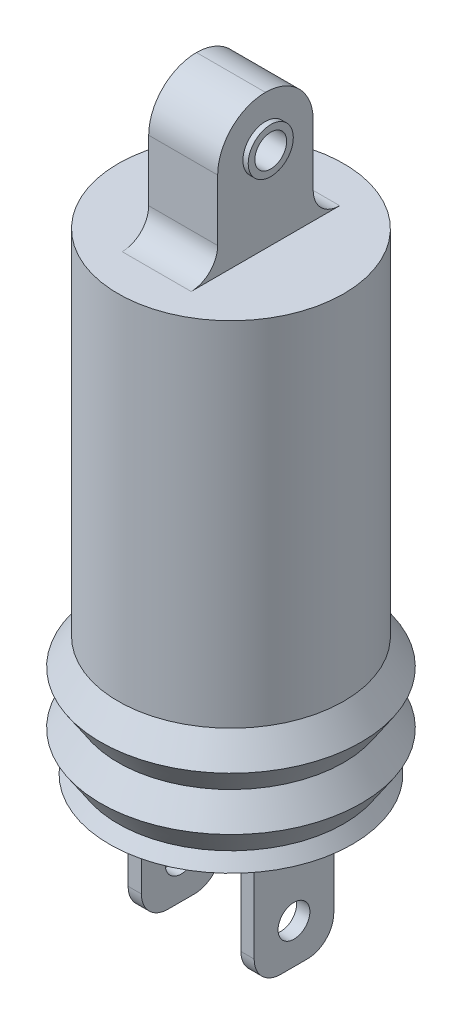
SolidWorks part; units mm, degrees
ref_plane "Płaszczyzna przednia" through (0, 0, 0) normal (0, 0, 1) x (1, 0, 0)
ref_plane "Płaszczyzna górna" through (0, 0, 0) normal (0, 1, 0) x (1, 0, 0)
ref_plane "Płaszczyzna prawa" through (0, 0, 0) normal (1, 0, 0) x (0, 0, -1)
sketch "Szkic1" plane through (0, 0, 0) normal (0, 0, 1) x (1, 0, 0)
  line L0 (-42.5, 0) -> (-42.5, 53)
  line L1 (0, -125) -> (0, 53) construction
  line L2 (-42.5, 53) -> (0, 53)
  line L5 (0, 53) -> (0, -125)
  line L6 (-45.8166, -125) -> (0, -125)
  line L14 (-42.5, -80) -> (-49.1332, -90)
  line L15 (-49.1332, -90) -> (-42.5, -100)
  line L16 (-42.5, -100) -> (-49.1332, -110)
  line L17 (-49.1332, -110) -> (-42.5, -120)
  line L18 (-42.5, -120) -> (-45.8166, -125)
  line L19 (-42.5, 0) -> (-42.5, -80)
  dimension "D1" = 42.5
  dimension "D2" = 53
  dimension "D7" = 125
revolve "Obrót1" add sketch "Szkic1" angle 360 about L1
sketch "Szkic2" plane through (0, 53, 0) normal (0, 1, 0) x (1, 0, 0)
  line L1 (-13, -18) -> (13, -18)
  line L2 (-13, -18) -> (-13, 18)
  line L3 (-13, 18) -> (13, 18)
  line L4 (13, -18) -> (13, 18)
  line L5 (-13, -18) -> (13, 18) construction
  line L6 (-13, 18) -> (13, -18) construction
  point P0 (0, 0)
  dimension "D1" = 26
  dimension "D2" = 36
extrude "Dodanie-wyciągnięcie1" add sketch "Szkic2" along normal blind 51
sketch "Szkic3" plane through (0, -125, 0) normal (0, -1, 0) x (1, 0, 0)
  line L1 (-23.75, -15) -> (23.75, -15)
  line L2 (-23.75, -15) -> (-23.75, 15)
  line L3 (-23.75, 15) -> (23.75, 15)
  line L4 (23.75, -15) -> (23.75, 15)
  line L5 (-23.75, -15) -> (23.75, 15) construction
  line L6 (-23.75, 15) -> (23.75, -15) construction
  point P0 (0, 0)
  dimension "D1" = 47.5
  dimension "D2" = 30
extrude "Dodanie-wyciągnięcie2" add sketch "Szkic3" along normal blind 5 contours L2 L3 L4 L1
sketch "Szkic4" plane through (0, -130, 0) normal (0, -1, 0) x (1, 0, 0)
  line L0 (-23.75, 15) -> (23.75, 15) construction
  line L1 (-23.75, -15) -> (-18.75, -15)
  line L2 (-23.75, -15) -> (-23.75, 15)
  line L3 (-23.75, 15) -> (-18.75, 15)
  line L4 (-18.75, -15) -> (-18.75, 15)
  line L6 (23.75, -15) -> (18.75, -15)
  line L7 (23.75, -15) -> (23.75, 15)
  line L8 (23.75, 15) -> (18.75, 15)
  line L9 (18.75, -15) -> (18.75, 15)
  dimension "D1" = 5
  dimension "D2" = 5
extrude "Dodanie-wyciągnięcie3" add sketch "Szkic4" along normal blind 46
sketch "Szkic5" plane through (23.75, 0, 0) normal (1, 0, 0) x (0, 0, -1)
  line L3 (15, -176) -> (-15, -176) construction
  line L4 (15, -176) -> (15, -125) construction
  circle A0 centre (0, -161) radius 6
  dimension "D1" = 12
  dimension "D2" = 15
  dimension "D3" = 15
extrude "Wytnij-wyciągnięcie1" cut sketch "Szkic5" against normal through all
sketch "Szkic6" plane through (13, 0, 0) normal (1, 0, 0) x (0, 0, -1)
  line L0 (-18, 104) -> (18, 104) construction
  line L1 (-18, 104) -> (-18, 53) construction
  circle A0 centre (0, 86) radius 6
  dimension "D1" = 12
  dimension "D2" = 18
  dimension "D3" = 18
extrude "Wytnij-wyciągnięcie2" cut sketch "Szkic6" against normal blind 46
sketch "Szkic8" plane through (13, 0, 0) normal (1, 0, 0) x (0, 0, -1)
  circle A0 centre (0, 86) radius 6
  circle A1 centre (0, 86) radius 6 construction
  circle A2 centre (0, 86) radius 8.5
  dimension "D1" = 12
  dimension "D2" = 17
extrude "Dodanie-wyciągnięcie4" add sketch "Szkic8" along normal blind 2
mirror "Lustro1" about plane through (0, 0, 0) normal (1, 0, 0) of "Dodanie-wyciągnięcie4"
fillet "Zaokrąglenie1" radius 18 2 edges at (0, 104, 18) (0, 104, -18)
fillet "Zaokrąglenie2" radius 10 2 edges at (0, 53, 18) (0, 53, -18)
fillet "Zaokrąglenie3" radius 10 4 edges at (-21.25, -176, 15) (21.25, -176, 15) (21.25, -176, -15) (-21.25, -176, -15)
